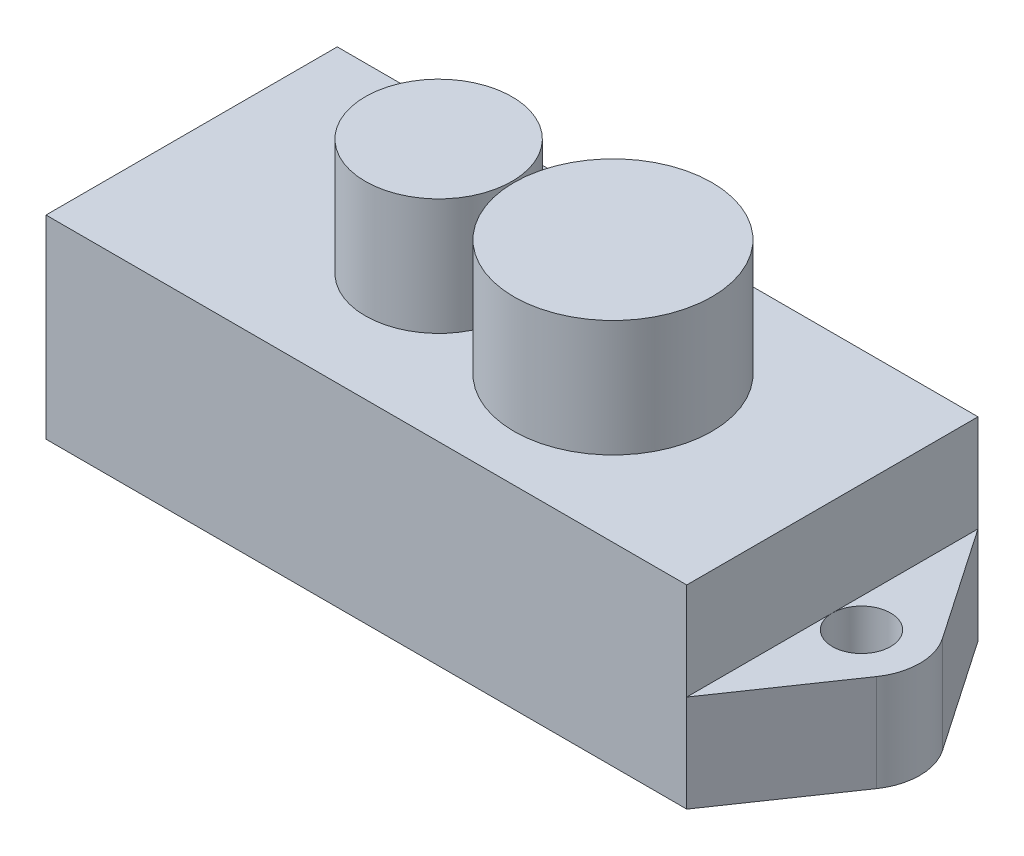
SolidWorks part; units mm, degrees
ref_plane "Front Plane" through (0, 0, 0) normal (0, 0, 1) x (1, 0, 0)
ref_plane "Top Plane" through (0, 0, 0) normal (0, 1, 0) x (1, 0, 0)
ref_plane "Right Plane" through (0, 0, 0) normal (1, 0, 0) x (0, 0, -1)
sketch "Sketch1" plane through (0, 0, 0) normal (0, 1, 0) x (1, 0, 0)
  line L0 (16.5, 0) -> (-15, 0) construction
  line L1 (-16.5, 7.5) -> (16.5, 7.5)
  line L2 (-16.5, 7.5) -> (-16.5, -7.5)
  line L3 (-16.5, -7.5) -> (16.5, -7.5)
  line L4 (16.5, 7.5) -> (16.5, -7.5)
  line L5 (-16.5, 7.5) -> (16.5, -7.5) construction
  line L6 (-16.5, -7.5) -> (16.5, 7.5) construction
  line L7 (0, 7.5) -> (0, -7.5) construction
  line L9 (-20.4752, 1.695) -> (-16.5, 7.5)
  line L10 (-20.4752, -1.695) -> (-16.5, -7.5)
  line L11 (-16.5, 7.5) -> (-16.5, -7.5)
  line L12 (16.5, 7.5) -> (16.5, -7.5)
  line L13 (20.4752, -1.695) -> (16.5, -7.5)
  line L14 (20.4752, 1.695) -> (16.5, 7.5)
  line L15 (16.5, 7.5) -> (16.5, -7.5)
  circle A0 centre (-3.7778, 0) radius 3.7778
  circle A1 centre (5.2, 0) radius 5.2
  arc A3 (-20.4752, 1.695) -> (-20.4752, -1.695) centre (-18, 0) ccw
  arc A5 (20.4752, 1.695) -> (20.4752, -1.695) centre (18, 0) cw
  point P0 (0, 0)
  dimension "D1" = 33
  dimension "D2" = 15
extrude "Boss-Extrude11" add sketch "Sketch1" along normal blind 5 contours L9 A3 L10 L2 | A5 L14 L4 L13 region at (-18.1531, 0, 0) region at (18.1531, 0, 0)
extrude "Boss-Extrude13" add sketch "Sketch1<5>" along normal blind 10 contours L4 L1 L2 L3 A0 A1 | A1 | A0 region at (0, 0, -7.1375) region at (-3.7778, 0, 0) region at (5.2, 0, 0)
sketch "Sketch1<5>" plane through (0, 0, 0) normal (0, 1, 0) x (1, 0, 0) same geometry as "Sketch1"
sketch "Sketch2" plane through (0, 5, 0) normal (0, 1, 0) x (1, 0, 0)
  circle A0 centre (-18, 0) radius 1.5
  circle A1 centre (18, 0) radius 1.5
extrude "Cut-Extrude1" cut sketch "Sketch2" against normal blind 5 contours A0 | A1
sketch "Sketch3" plane through (0, 10, 0) normal (0, 1, 0) x (1, 0, 0)
  circle A0 centre (-3.7778, 0) radius 3.7778
  circle A1 centre (5.2, 0) radius 5.2
  circle A2 centre (5.2, 0) radius 5.1
extrude "Boss-Extrude18" add sketch "Sketch3" along normal blind 6 contours A0 region at (-3.7778, 10, 0)
extrude "Boss-Extrude22" add sketch "Sketch3<5>" along normal blind 6 contours A2
sketch "Sketch3<5>" plane through (0, 10, 0) normal (0, 1, 0) x (1, 0, 0) same geometry as "Sketch3"
